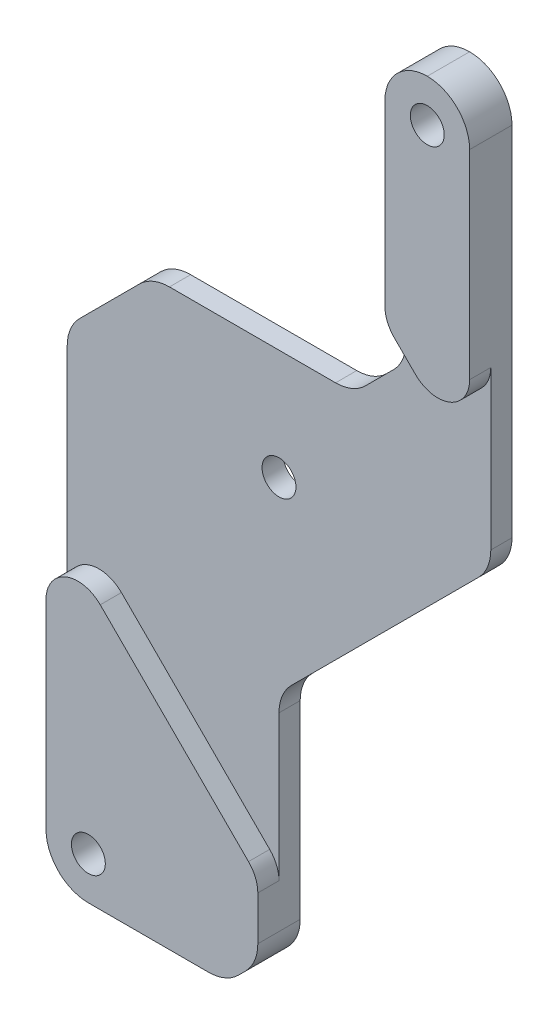
SolidWorks part; units mm, degrees
material "Thornel Mat VMA"
ref_plane "Front Plane" through (0, 0, 0) normal (0, 0, 1) x (1, 0, 0)
ref_plane "Top Plane" through (0, 0, 0) normal (0, 1, 0) x (1, 0, 0)
ref_plane "Right Plane" through (0, 0, 0) normal (1, 0, 0) x (0, 0, -1)
sketch "Sketch1" plane through (0, 0, 0) normal (0, 0, 1) x (1, 0, 0)
  line L0 (-12, -87.8) -> (12, -87.8)
  line L1 (12, -87.8) -> (12, -56.4)
  line L2 (12, -56.4) -> (20, -56.4)
  line L3 (20, -56.4) -> (20, -95.8)
  line L5 (0, -115.8) -> (0, -140)
  line L6 (0, -140) -> (-20, -140)
  line L7 (-20, -140) -> (-20, -95.8)
  line L8 (-20, -95.8) -> (-12, -87.8)
  line L10 (-12, -86.9716) -> (-12, -87.8) construction
  line L11 (-12, -87.8) -> (-12.5858, -88.3858) construction
  line L12 (-12.5858, -88.3858) -> (-19.4142, -95.2142) construction
  line L13 (-20, -100.9983) -> (-20, -60.2497) construction
  line L14 (20, -60.2536) -> (20, -100.9506) construction
  line L15 (12, -58.8284) -> (12, -86.9716) construction
  line L16 (0, -115.8) -> (20, -95.8)
  line L17 (20, -100.9506) -> (20, -135.91) construction
  line L18 (0, -55) -> (0, 55) construction
  line L19 (-16, -140) -> (-27.1716, -140) construction
  line L20 (19.4142, -95.2142) -> (20, -95.8) construction
  line L21 (12.5858, -88.3858) -> (19.4142, -95.2142) construction
  dimension "D1" = 45
  dimension "D2" = 4
extrude "Boss-Extrude1" add sketch "Sketch1" along normal blind 4 contours L16 L3 L2 L1 L0 L8 L7 L6 L5
fillet "Fillet1" radius 4 3 edges at (12, -56.4, 2) (20, -56.4, 2) (-20, -140, 2)
chamfer "Chamfer1" distance 3 angle 45 1 edges at (0, -140, 2)
chamfer "Chamfer2" distance 5 angle 45 1 edges at (12, -87.8, 2)
fillet "Fillet2" radius 4 8 edges at (0, -115.8, 2) (20, -95.8, 2) (7, -87.8, 2) (-12, -87.8, 2) (-20, -95.8, 2) (-3, -140, 2) (0, -137, 2) (12, -82.8, 2)
sketch "Sketch2" plane through (0, 0, 4) normal (0, 0, 1) x (1, 0, 0)
  line L0 (-16, -136) -> (16, -60.4) construction
  circle A0 centre (0, -98.2) radius 1.6
  dimension "D1" = 3.2
extrude "Cut-Extrude1" cut sketch "Sketch2" against normal through all
sketch "Sketch3" plane through (0, 0, 4) normal (0, 0, 1) x (1, 0, 0)
  line L0 (0, -129.9421) -> (31.7421, -98.2)
  line L1 (0, -129.9421) -> (-31.7421, -98.2)
  line L2 (31.7421, -98.2) -> (0, -66.4579)
  line L3 (-31.7421, -98.2) -> (0, -66.4579)
  line L4 (0, -129.9421) -> (0, -66.4579) construction
  line L5 (31.7421, -98.2) -> (-31.7421, -98.2) construction
  line L6 (0, -82.9497) -> (0, 82.9497) construction
  line L7 (-1.1716, -114.6284) -> (-18.8284, -96.9716) construction
  circle A1 centre (0, -98.2) radius 1.6 construction
  point P1 (0, -98.2)
  point P12 (-15.8711, -114.0711)
  dimension "D1" = 10
extrude "Cut-Extrude2" cut sketch "Sketch3" against normal blind 2
fillet "Fillet3" radius 3 4 edges at (0, -129.9421, 3) (12, -78.4579, 3) (20, -86.4579, 3) (-20, -109.9421, 3)
sketch "Sketch4" plane through (0, 0, 4) normal (0, 0, 1) x (1, 0, 0)
  circle A0 centre (-16, -136) radius 1.6
  circle A1 centre (-16, -136) radius 1.6 construction
  circle A2 centre (16, -60.4) radius 1.6
  arc A3 (17.6, -60.4) -> (14.4, -60.4) centre (16, -60.4) ccw construction
extrude "Cut-Extrude3" cut sketch "Sketch4" against normal through all
